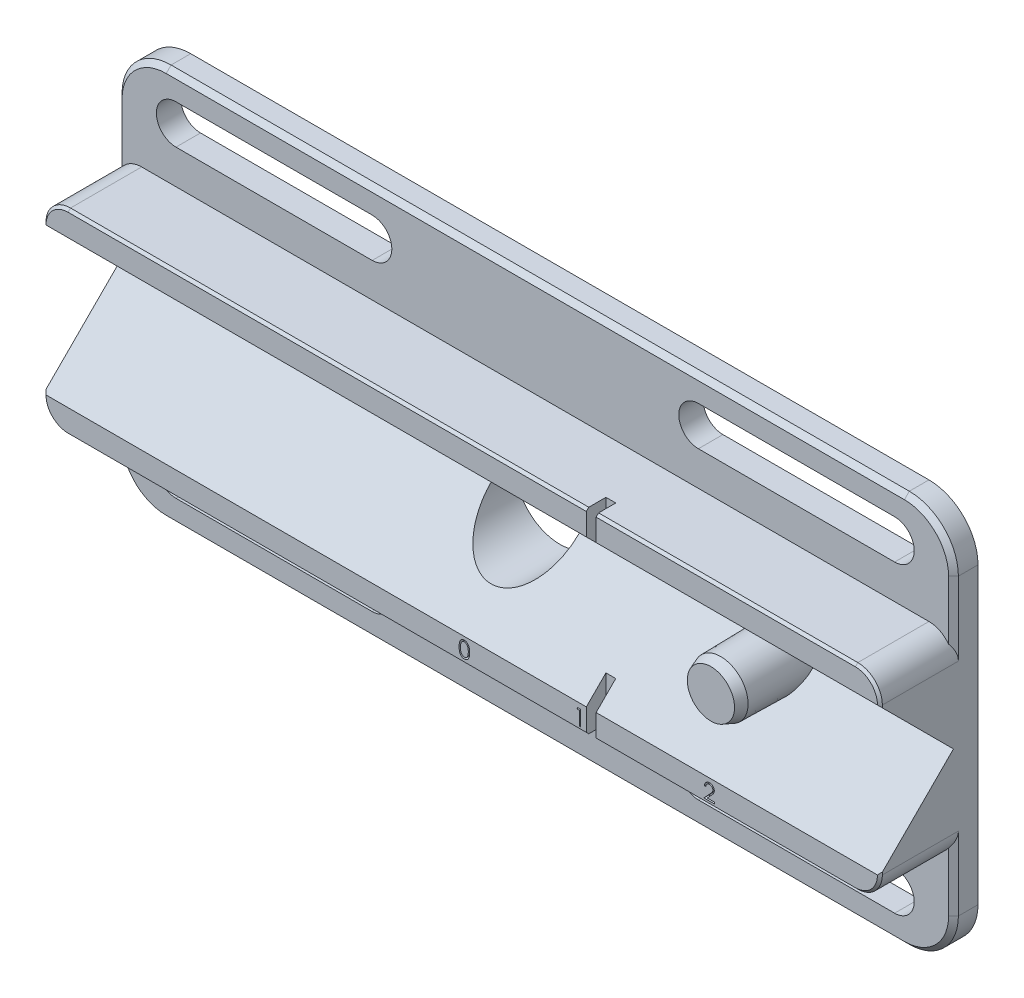
SolidWorks part; units mm, degrees
ref_plane "Front Plane" through (0, 0, 0) normal (0, 0, 1) x (1, 0, 0)
ref_plane "Top Plane" through (0, 0, 0) normal (0, 1, 0) x (1, 0, 0)
ref_plane "Right Plane" through (0, 0, 0) normal (1, 0, 0) x (0, 0, -1)
sketch "Sketch2" plane through (0, 0, 0) normal (0, 0, 1) x (1, 0, 0)
  line L0 (129.6728, 828.7945) -> (1132.3395, 828.7945) construction
  line L1 (0, 87) -> (0, 31) construction
  line L2 (8.25, 87) -> (8.25, 31)
  line L3 (-8.25, 87) -> (-8.25, 31)
  line L4 (0, -33) -> (0, -57) construction
  line L5 (8.25, -33) -> (8.25, -57)
  line L6 (-8.25, -33) -> (-8.25, -57)
  line L7 (57, 87) -> (57, -57) construction
  line L8 (65.25, 87) -> (65.25, -57)
  line L9 (48.75, 87) -> (48.75, -57)
  line L10 (-57, -57) -> (-57, 87) construction
  line L11 (-65.25, -57) -> (-65.25, 87)
  line L12 (-48.75, -57) -> (-48.75, 87)
  line L14 (-85, 110) -> (85, 110)
  line L15 (-85, 110) -> (-85, -82)
  line L16 (-85, -82) -> (85, -82)
  line L17 (85, 110) -> (85, -82)
  circle A0 centre (0, 0) radius 10.5
  arc A1 (8.25, 87) -> (-8.25, 87) centre (0, 87) ccw
  arc A2 (-8.25, 31) -> (8.25, 31) centre (0, 31) ccw
  arc A3 (8.25, -33) -> (-8.25, -33) centre (0, -33) ccw
  arc A4 (-8.25, -57) -> (8.25, -57) centre (0, -57) ccw
  arc A5 (65.25, 87) -> (48.75, 87) centre (57, 87) ccw
  arc A6 (48.75, -57) -> (65.25, -57) centre (57, -57) ccw
  arc A7 (-65.25, -57) -> (-48.75, -57) centre (-57, -57) ccw
  arc A8 (-48.75, 87) -> (-65.25, 87) centre (-57, 87) ccw
  point P7 (0, 59)
  point P12 (0, -45)
  point P21 (57, 15)
  point P26 (-57, 15)
  dimension "D1" = 21
  dimension "D2" = 16.5
  dimension "D3" = 31
  dimension "D4" = 56
  dimension "D5" = 16.5
  dimension "D6" = 33
  dimension "D7" = 24
  dimension "D8" = 16.5
  dimension "D9" = 16.5
  dimension "D10" = 57
  dimension "D11" = 57
  dimension "D12" = 85
  dimension "D13" = 85
  dimension "D14" = 110
  dimension "D15" = 82
sketch "Sketch3" plane through (0, 0, 0) normal (0, 0, 1) x (1, 0, 0)
  line L1 (-85.25, 20) -> (85.25, 20)
  line L3 (-85.25, -20) -> (85.25, -20)
  line L6 (0, 33) -> (0, -33) construction
  line L7 (-116.9037, 0) -> (116.0814, 0) construction
  line L8 (-85.25, 20) -> (-85.25, -20)
  line L9 (85.25, 20) -> (85.25, -20)
  line L10 (65.25, 87) -> (65.25, -57) construction
  line L11 (-65.25, -57) -> (-65.25, 87) construction
  point P4 (85.25, 0)
  point P14 (0, 0)
  dimension "D1" = 40
  dimension "D2" = 20
  dimension "D3" = 20
extrude "Boss-Extrude1" add sketch "Sketch3" along normal blind 20
sketch "Sketch11" plane through (0, 0, 0) normal (0, 0, 1) x (1, 0, 0)
  line L0 (85.25, -20) -> (85.25, 20) construction
  line L1 (-75.25, 40) -> (75.25, 40)
  line L2 (-85.25, 30) -> (-85.25, -30)
  line L3 (-75.25, -40) -> (75.25, -40)
  line L4 (85.25, 30) -> (85.25, -30)
  line L5 (-85.25, 20) -> (-85.25, -20) construction
  line L6 (85.25, 20) -> (-85.25, 20) construction
  line L7 (-85.25, -20) -> (85.25, -20) construction
  arc A0 (-85.25, -30) -> (-75.25, -40) centre (-75.25, -30) ccw
  arc A1 (75.25, -40) -> (85.25, -30) centre (75.25, -30) ccw
  arc A2 (75.25, 40) -> (85.25, 30) centre (75.25, 30) cw
  arc A3 (-75.25, 40) -> (-85.25, 30) centre (-75.25, 30) ccw
  dimension "D3" = 10
  dimension "D1" = 20
  dimension "D2" = 20
extrude "Boss-Extrude4" add sketch "Sketch11" along normal blind 5
sketch "Sketch4" plane through (85.25, 0, 0) normal (1, 0, 0) x (0, 0, -1)
  line L0 (-20, 15) -> (-5, 0)
  line L2 (-5, 0) -> (-20, -15)
  line L4 (0, 87) -> (0, -57) construction
  line L5 (-20, 15) -> (-20, -15)
  line L7 (-20, -20) -> (-20, 20) construction
  line L8 (0, -30) -> (0, 30) construction
  point P4 (0, 0)
  point P13 (0, 0)
  dimension "D1" = 5
  dimension "D2" = 5
  dimension "D3" = 5
extrude "Cut-Extrude1" cut sketch "Sketch4" against normal up to next
sketch "Sketch8" plane through (0, 0, 0) normal (0, 0, 1) x (1, 0, 0)
  line L0 (-85.25, 0) -> (85.25, 0) construction
  circle A0 centre (50.8, 0) radius 5.9
  point P2 (0, 0)
  dimension "D1" = 11.8
  dimension "D2" = 50.8
extrude "Boss-Extrude3" add sketch "Sketch8" along normal blind 20 draft 1
chamfer "Chamfer1" distance 2 angle 20 1 edges at (56.3509, 0, 20)
fillet "Fillet1" radius 5 4 edges at (-85.25, 20, 12.5) (-85.25, -20, 12.5) (85.25, 20, 12.5) (85.25, -20, 12.5)
sketch "Sketch9" plane through (0, 0, 20) normal (0, 0, 1) x (1, 0, 0)
  line L0 (80.25, 20) -> (-80.25, 20) construction
  line L1 (25.4, 20) -> (27.4, 20)
  line L2 (25.4, 20) -> (25.4, -20)
  line L3 (25.4, -20) -> (27.4, -20)
  line L4 (27.4, 20) -> (27.4, -20)
  line L5 (-80.25, -20) -> (80.25, -20) construction
  dimension "D1" = 2
  dimension "D2" = 25.4
extrude "Cut-Extrude4" cut sketch "Sketch9" against normal blind 4
sketch "Sketch10" plane through (0, 0, 20) normal (0, 0, 1) x (1, 0, 0)
  text T0 "0"
  text T1 "1"
  text T2 "2"
  point P2 (28.4519, -19.9919)
  point P4 (49.6111, -19.5855)
  point P5 (0, 0)
  point P6 (49.2512, -19.9919)
  point P7 (0, 0)
extrude "Cut-Extrude5" cut sketch "Sketch10" against normal blind 1
sketch "Sketch12" plane through (0, 0, 0) normal (0, 0, -1) x (-1, 0, 0)
  circle A0 centre (0, 0) radius 9
  dimension "D1" = 18
extrude "Cut-Extrude6" cut sketch "Sketch12" against normal through all
sketch "Sketch13" plane through (0, 0, 5) normal (0, 0, 1) x (1, 0, 0)
  line L0 (-73.25, 31) -> (-33.25, 31) construction
  line L1 (-73.25, 35) -> (-33.25, 35)
  line L2 (-73.25, 27) -> (-33.25, 27)
  line L3 (-105.2694, 0) -> (102.6251, 0) construction
  line L4 (0, 56.9598) -> (0, -64.3855) construction
  line L5 (-85.25, 30) -> (-85.25, 15) construction
  line L6 (75.25, 40) -> (-75.25, 40) construction
  line L7 (73.25, 31) -> (33.25, 31) construction
  line L8 (73.25, 35) -> (33.25, 35)
  line L9 (73.25, 27) -> (33.25, 27)
  line L10 (73.25, -31) -> (33.25, -31) construction
  line L11 (73.25, -35) -> (33.25, -35)
  line L12 (73.25, -27) -> (33.25, -27)
  line L13 (-73.25, -31) -> (-33.25, -31) construction
  line L14 (-73.25, -35) -> (-33.25, -35)
  line L15 (-73.25, -27) -> (-33.25, -27)
  arc A0 (-73.25, 35) -> (-73.25, 27) centre (-73.25, 31) ccw
  arc A1 (-33.25, 27) -> (-33.25, 35) centre (-33.25, 31) ccw
  arc A2 (73.25, 35) -> (73.25, 27) centre (73.25, 31) cw
  arc A3 (33.25, 27) -> (33.25, 35) centre (33.25, 31) cw
  arc A4 (73.25, -35) -> (73.25, -27) centre (73.25, -31) ccw
  arc A5 (33.25, -27) -> (33.25, -35) centre (33.25, -31) ccw
  arc A6 (-73.25, -35) -> (-73.25, -27) centre (-73.25, -31) cw
  arc A7 (-33.25, -27) -> (-33.25, -35) centre (-33.25, -31) cw
  point P2 (-53.25, 31)
  point P18 (53.25, 31)
  point P25 (53.25, -31)
  point P32 (-53.25, -31)
  dimension "D1" = 8
  dimension "D2" = 12
  dimension "D3" = 40
  dimension "D4" = 5
extrude "Cut-Extrude7" cut sketch "Sketch13" against normal through all
chamfer "Chamfer2" distance 1 angle 45 10 edges at (85.25, 22.5, 5) (-85.25, 22.5, 5) (82.3211, 37.0711, 5) (-82.3211, 37.0711, 5) (0, 40, 5) (-85.25, -22.5, 5) (85.25, -22.5, 5) (-82.3211, -37.0711, 5) (82.3211, -37.0711, 5) (0, -40, 5)
chamfer "Chamfer3" distance 0.5 angle 45 8 edges at (-83.7855, -18.5355, 20) (-27.425, -20, 20) (83.7855, -18.5355, 20) (53.825, -20, 20) (83.7855, 18.5355, 20) (53.825, 20, 20) (-83.7855, 18.5355, 20) (-27.425, 20, 20)
